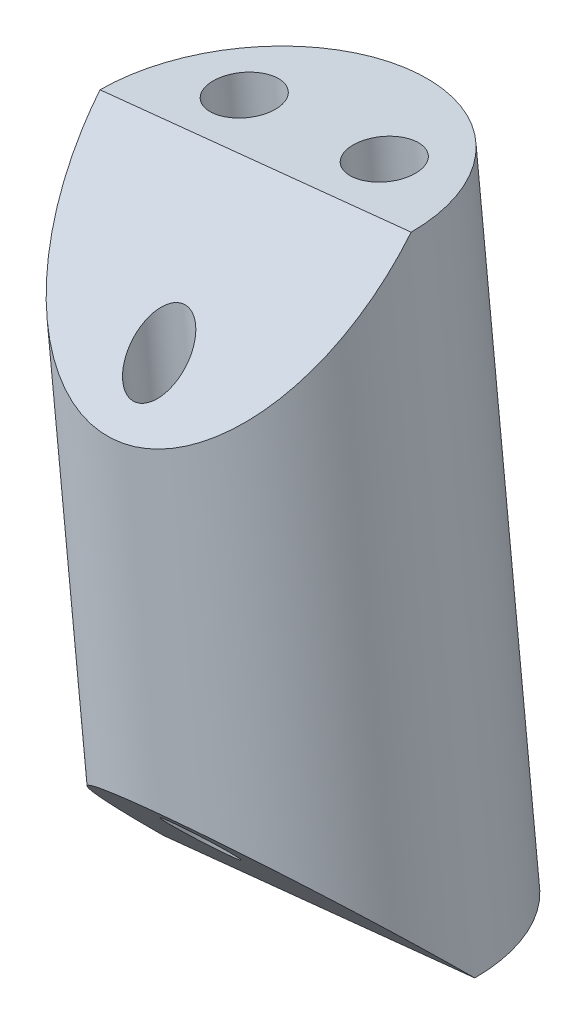
SolidWorks part; units mm, degrees
ref_plane "Front Plane" through (0, 0, 0) normal (0, 0, 1) x (1, 0, 0)
ref_plane "Top Plane" through (0, 0, 0) normal (0, 1, 0) x (1, 0, 0)
ref_plane "Right Plane" through (0, 0, 0) normal (1, 0, 0) x (0, 0, -1)
sketch "Sketch2" plane through (0, 0, 0) normal (0, 0, 1) x (1, 0, 0)
  line L0 (0, 0) -> (90, 0)
  line L1 (90, 0) -> (90, 120)
  line L2 (90, 120) -> (0, 120)
  line L3 (0, 120) -> (0, 0)
  line L4 (0, 120) -> (-10, 120)
  line L5 (-10, 120) -> (-10, 16.9491)
  line L6 (-10, 120) -> (57.5, 127)
  line L7 (57.5, 127) -> (90, 124)
  line L8 (90, 120) -> (99, 60)
  line L10 (90, 124) -> (90, 120)
  line L11 (5.9147, 0) -> (5.9147, -25)
  line L12 (5.9147, -25) -> (-4.0853, -25)
  line L13 (-4.0853, -29) -> (-4.0853, 0)
  line L14 (80, 0) -> (80, -25)
  line L15 (80, -25) -> (90, -25)
  line L16 (90, -29) -> (90, 0)
  line L17 (15.7927, 122.6748) -> (5.4776, 222.1414)
  line L18 (5.4776, 222.1414) -> (21.3923, 223.7918)
  line L19 (21.3923, 223.7918) -> (31.7073, 124.3252)
  line L20 (7.6492, 201.201) -> (23.5639, 202.8514)
  line L21 (10.9066, 169.7905) -> (26.8212, 171.441)
  line L22 (-10, 120) -> (-20.0396, 216.8108)
  line L23 (-20.0396, 216.8108) -> (-4.125, 218.4612)
  line L24 (-4.125, 218.4612) -> (5.9147, 121.6504)
  line L25 (-17.926, 196.4296) -> (-2.0114, 198.08)
  line L26 (-14.7556, 165.8578) -> (1.159, 167.5082)
  line L27 (57.5, 127) -> (46.9095, 229.1223)
  line L28 (46.9095, 229.1223) -> (30.9949, 227.4719)
  line L29 (30.9949, 227.4719) -> (41.5853, 125.3496)
  line L30 (33.2245, 205.9725) -> (49.1391, 207.6229)
  line L31 (36.5688, 173.7233) -> (52.4835, 175.3737)
  line L34 (90, 124) -> (99.1917, 223.5767)
  line L35 (99.1917, 223.5767) -> (83.2594, 225.0473)
  line L36 (83.2594, 225.0473) -> (74.0677, 125.4707)
  line L38 (81.3243, 204.0838) -> (97.2566, 202.6132)
  line L39 (78.4217, 172.6386) -> (94.354, 171.1679)
  line L40 (62.4078, 79.6749) -> (57.5, 127) construction
  line L41 (41.5853, 125.3496) -> (46.4931, 78.0244) construction
  line L42 (46.4931, 78.0244) -> (62.4078, 79.6749) construction
  line L43 (31.7073, 124.3252) -> (36.6151, 77.0001) construction
  line L44 (36.6151, 77.0001) -> (20.7005, 75.3496) construction
  line L45 (20.7005, 75.3496) -> (15.7927, 122.6748) construction
  line L46 (5.9147, 121.6504) -> (10.8224, 74.3253) construction
  line L47 (10.8224, 74.3253) -> (-5.0922, 72.6749) construction
  line L48 (-5.0922, 72.6749) -> (-10, 120) construction
  line L49 (74.0677, 125.4707) -> (69.6944, 78.0931) construction
  line L50 (69.6944, 78.0931) -> (85.7624, 78.0931) construction
  line L51 (85.7624, 78.0931) -> (90, 124) construction
  line L52 (-12.0823, 217.636) -> (10.4873, 0) construction
  line L53 (13.4349, 222.9666) -> (36.5574, 0) construction
  line L54 (38.9522, 228.2971) -> (62.6275, 0) construction
  line L55 (91.2256, 224.312) -> (70.5198, 0) construction
  line L59 (99, 60) -> (93.5277, 44.9649)
  line L60 (99, 60) -> (169.4769, 34.3485)
  line L61 (169.4769, 34.3485) -> (164.0046, 19.3134)
  line L62 (164.0046, 19.3134) -> (93.5277, 44.9649)
  line L63 (90, -2) -> (100, -2)
  line L64 (141.2862, 44.6091) -> (135.8138, 29.574)
  line L65 (99, 60) -> (55.7741, 75.7329) construction
  line L66 (55.7741, 75.7329) -> (50.3018, 60.6978) construction
  line L67 (100, -2) -> (100, -29)
  line L70 (-4.0853, -2) -> (-14.0853, -2)
  line L71 (-14.0853, -2) -> (-14.0853, -29)
  line L74 (-4.0853, 0) -> (0, 0)
  line L75 (-14.0853, -29) -> (-14.0853, -112.587)
  line L76 (-14.0853, -112.587) -> (100, -112.587)
  line L77 (100, -112.587) -> (100, -29)
  line L78 (-14.0853, -29) -> (100, -29)
  line L79 (-14.0853, -14.5) -> (100, -14.5) construction
  line L80 (31.7073, -112.587) -> (31.7073, -122.6232)
  line L81 (31.7073, -122.6232) -> (42.9573, -122.6232)
  line L82 (42.9573, -122.6232) -> (42.9573, -112.587)
  line L83 (-14.0853, -112.587) -> (-88.3667, -112.587)
  line L84 (-88.3667, -112.587) -> (-88.3667, -128.2699)
  line L85 (-88.3667, -128.2699) -> (169.4958, -128.2699)
  line L86 (169.4958, -128.2699) -> (169.4958, -112.587)
  line L87 (169.4958, -112.587) -> (100, -112.587)
  line L88 (90, 60) -> (-10, 60) construction
  line L89 (50.3018, 60.6978) -> (93.5277, 44.9649) construction
  line L90 (87.2806, 55.7521) -> (166.7408, 26.8309) construction
  line L91 (87.2806, 55.7521) -> (82.1749, 52.5336) construction
  line L92 (82.1749, 52.5336) -> (77.3257, 0) construction
  line L93 (83.1185, 56.6957) -> (86.337, 51.59) construction
  arc A0 (-10, 16.9491) -> (-4.0853, 0) centre (14.9876, 16.1624) ccw
  arc A1 (93.5277, 44.9649) -> (90, 0) centre (-126.4069, 39.5988) cw
  point P42 (41.1818, 206.7977)
  point P100 (84.7278, 54.1428)
  point P101 (84.7278, 54.1428)
  dimension "D11" = 47.3684
  dimension "D35" = 9
  dimension "D32" = 220
  dimension "D36" = 25
  dimension "D1" = 120
  dimension "D2" = 90
  dimension "D3" = 10
  dimension "D5" = 67.862
  dimension "D6" = 7
  dimension "D7" = 4
  dimension "D8" = 16
  dimension "D9" = 16
  dimension "D10" = 100
  dimension "D12" = 31.5789
  dimension "D13" = 16
  dimension "D14" = 16
  dimension "D15" = 16
  dimension "D16" = 25.7927
  dimension "D17" = 100
  dimension "D18" = 21.0526
  dimension "D19" = 31.5789
  dimension "D20" = 97.33
  dimension "D21" = 102.67
  dimension "D22" = 20.4905
  dimension "D23" = 30.7358
  dimension "D24" = 21.6147
  dimension "D25" = 32.4221
  dimension "D26" = 25
  dimension "D28" = 25
  dimension "D29" = 75
  dimension "D30" = 47.5789
  dimension "D31" = 30
  dimension "D33" = 46
  dimension "D34" = 20
  dimension "D37" = 2
  dimension "D38" = 2
  dimension "D39" = 27
  dimension "D40" = 10
  dimension "D41" = 10
  dimension "D42" = 27
  dimension "D43" = 14.5
  dimension "D44" = 127.5
ref_plane "Plane1" through (87.2806, 55.7521, 0) normal (-0.846, -0.5333, 0) x (0, 0, 1)
ref_plane "Plane2" through (82.1749, 52.5336, 0) normal (-0.0919, -0.9958, 0) x (-0.9958, 0.0919, 0)
ref_plane "Plane3" through (91.2256, 224.312, 0) normal (-0.0919, -0.9958, 0) x (-0.9958, 0.0919, 0)
ref_plane "Plane4" through (38.9522, 228.2971, 0) normal (0.1032, -0.9947, 0) x (-0.9947, -0.1032, 0)
ref_plane "Plane5" through (13.4349, 222.9666, 0) normal (0.1032, -0.9947, 0) x (-0.9947, -0.1032, 0)
ref_plane "Plane7" through (166.7408, 26.8309, 0) normal (0.9397, -0.342, 0) x (0, 0, -1)
ref_plane "Plane8" through (110.4217, -40.1902, 0) normal (0.9397, -0.342, 0) x (0, 0, -1)
ref_plane "Plane9" through (19.3664, 209.803, 0) normal (-0.0919, -0.9958, 0) x (-0.9958, 0.0919, 0)
ref_plane "Plane10" through (16.4638, 178.3578, 0) normal (-0.0919, -0.9958, 0) x (-0.9958, 0.0919, 0)
ref_plane "Plane11" through (-20.7793, 200.3721, 0) normal (0.1032, -0.9947, 0) x (-0.9947, -0.1032, 0)
ref_plane "Plane12" through (-17.435, 168.1229, 0) normal (0.1032, -0.9947, 0) x (-0.9947, -0.1032, 0)
ref_plane "Plane13" through (-20.5619, 198.2754, 0) normal (0.1032, -0.9947, 0) x (-0.9947, -0.1032, 0)
ref_plane "Plane14" through (-17.3045, 166.8649, 0) normal (0.1032, -0.9947, 0) x (-0.9947, -0.1032, 0)
ref_plane "Plane15" through (-12.0823, 217.636, 0) normal (0.1032, -0.9947, 0) x (-0.9947, -0.1032, 0)
ref_plane "Plane16" through (-20.3445, 196.1788, 0) normal (0.1032, -0.9947, 0) x (-0.9947, -0.1032, 0)
ref_plane "Plane17" through (-17.1741, 165.607, 0) normal (0.1032, -0.9947, 0) x (-0.9947, -0.1032, 0)
ref_plane "Plane18" through (12.1098, 131.1899, 0) normal (-0.0919, -0.9958, 0) x (-0.9958, 0.0919, 0)
ref_plane "Plane19" through (-12.4184, 119.7492, 0) normal (0.1032, -0.9947, 0) x (-0.9947, -0.1032, 0)
ref_plane "Plane20" through (0, 0, 0) normal (0, 0, 1) x (0.1032, -0.9947, 0)
ref_plane "Plane21" through (0, 0, 0) normal (0, 0, 1) x (-0.0919, -0.9958, 0)
ref_plane "Plane22" through (10.3758, 1.076, 0) normal (-0.9947, -0.1032, 0) x (0.1032, -0.9947, 0)
ref_plane "Plane23" through (36.1684, 3.7508, 0) normal (-0.9947, -0.1032, 0) x (0.1032, -0.9947, 0)
ref_plane "Plane24" through (61.9611, 6.4256, 0) normal (-0.9947, -0.1032, 0) x (0.1032, -0.9947, 0)
ref_plane "Plane25" through (69.924, -6.4545, 0) normal (-0.9958, 0.0919, 0) x (-0.0919, -0.9958, 0)
sketch "Sketch3" plane through (-20.3445, 196.1788, 0) normal (0.1032, -0.9947, 0) x (-0.9947, -0.1032, 0)
  line L0 (-2.4314, 0) -> (-18.4314, 0) construction
  circle A0 centre (-10.4314, 0) radius 8
  dimension "D1" = 16
extrude "Boss-Extrude1" add sketch "Sketch3" along normal blind 31.5789
sketch "Sketch4" plane through (10.3758, 1.076, 0) normal (-0.9947, -0.1032, 0) x (0.1032, -0.9947, 0)
  line L0 (-197.2309, 0) -> (-189.2309, 8)
  line L1 (-197.2309, 8) -> (-197.2309, -8) construction
  line L2 (-165.6519, 8) -> (-197.2309, 8) construction
  line L3 (-189.2309, 8) -> (-197.2309, 8)
  line L4 (-197.2309, 8) -> (-197.2309, 0)
  line L5 (-173.6519, 8) -> (-165.6519, 8)
  line L6 (-165.6519, 8) -> (-165.6519, 0)
  line L7 (-217.7214, 0) -> (1.0818, 0) construction
  line L8 (-165.6519, 0) -> (-173.6519, 8)
  dimension "D1" = 45
  dimension "D2" = 45
extrude "Cut-Extrude1" cut sketch "Sketch4" against normal through all and the other way through all
sketch "Sketch5" plane through (10.3758, 1.076, 0) normal (-0.9947, -0.1032, 0) x (0.1032, -0.9947, 0)
  line L0 (-165.6519, 0) -> (-169.6519, 4)
  line L1 (-165.6519, 0) -> (-173.6519, 8) construction
  line L2 (-169.6519, 4) -> (-161.6519, 4)
  line L3 (-161.6519, 4) -> (-161.6519, 0)
  line L4 (-213.7055, 0) -> (7.2742, 0) construction
  line L6 (-165.6519, 0) -> (-161.6519, 4) construction
  line L7 (-161.6519, 0) -> (-165.6519, -4)
  line L8 (-165.6519, -8) -> (-165.6519, 0) construction
  line L9 (-165.6519, 0) -> (-165.6519, -4)
  dimension "D1" = 4
  dimension "D2" = 45
sketch "Sketch7" plane through (10.3758, 1.076, 0) normal (-0.9947, -0.1032, 0) x (0.1032, -0.9947, 0)
  line L0 (-193.2309, 4) -> (-197.2309, 0)
  line L1 (-217.7214, 0) -> (1.0818, 0) construction
  line L4 (-197.2309, -4) -> (-197.2309, 0)
  line L5 (-193.2309, 4) -> (-193.2309, 0)
  arc A0 (-197.2309, -4) -> (-193.2309, 0) centre (-197.2309, 0) ccw
  dimension "D1" = 4
  dimension "D2" = 4
sketch "Sketch8" plane through (-20.3445, 196.1788, 0) normal (-0.1032, 0.9947, 0) x (0.9947, 0.1032, 0)
  line L0 (2.4314, 0) -> (18.4314, 0) construction
  circle A0 centre (10.4314, -5.5) radius 1.4
  circle A1 centre (6.8314, 3) radius 1.6
  circle A2 centre (14.0314, 3) radius 1.6
  point P9 (10.4314, 0)
  dimension "D1" = 3.2
  dimension "D2" = 3.2
  dimension "D3" = 2.8
  dimension "D4" = 3
  dimension "D5" = 5.5
  dimension "D6" = 3.6
  dimension "D7" = 3.6
  dimension "D8" = 3
extrude "Cut-Extrude3" cut sketch "Sketch8" against normal through all and the other way through all
sketch "Sketch9" plane through (-20.3445, 196.1788, 0) normal (-0.1032, 0.9947, 0) x (0.9947, 0.1032, 0)
  line L0 (4.5289, 5.4) -> (16.3339, 5.4)
  line L1 (-101.1265, 0) -> (155.3606, 0) construction
  arc A0 (18.4314, 0) -> (2.4314, 0) centre (10.4314, 0) ccw construction
  arc A1 (4.5289, 5.4) -> (16.3339, 5.4) centre (10.4314, 0) cw
  dimension "D1" = 5.4
